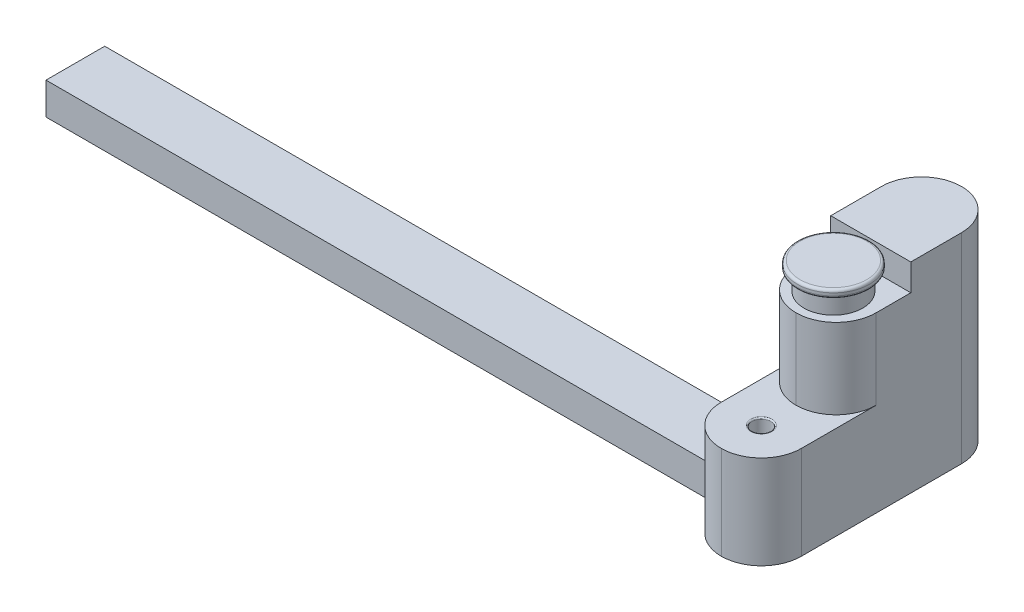
SolidWorks part; units mm, degrees
ref_plane "Front Plane" through (0, 0, 0) normal (0, 0, 1) x (1, 0, 0)
ref_plane "Top Plane" through (0, 0, 0) normal (0, 1, 0) x (1, 0, 0)
ref_plane "Right Plane" through (0, 0, 0) normal (1, 0, 0) x (0, 0, -1)
sketch "Sketch1" plane through (0, 0, 0) normal (1, 0, 0) x (0, 0, -1)
  line L1 (0, 0) -> (11, 0)
  line L2 (0, 0) -> (0, -6)
  line L3 (0, -6) -> (11, -6)
  line L4 (11, 0) -> (11, -6)
  dimension "D1" = 11
  dimension "D2" = 6
extrude "Boss-Extrude1" add sketch "Sketch1" along normal blind 124 from offset 73.5 offset against normal yes
sketch "Sketch2" plane through (50.5, 0, 0) normal (1, 0, 0) x (0, 0, -1)
  line L9 (-5, -9) -> (40, -9)
  line L10 (-5, -9) -> (-5, 28.5)
  line L11 (-5, 28.5) -> (40, 28.5)
  line L12 (40, -9) -> (40, 28.5)
  line L13 (-5, 8.5) -> (9, 8.5)
  line L14 (-5, 8.5) -> (-5, 28.5)
  line L15 (-5, 28.5) -> (9, 28.5)
  line L16 (9, 8.5) -> (9, 23.5)
  line L17 (9, 23.5) -> (23, 23.5)
  line L19 (9, 28.5) -> (23, 28.5)
  line L20 (23, 23.5) -> (23, 28.5)
  line M1 (0, 0) -> (0, -6)
  line M2 (0, -6) -> (11, -6)
  line M3 (11, -6) -> (11, 0)
  line M4 (11, 0) -> (0, 0)
  dimension "D1" = 5
  dimension "D2" = 9
  dimension "D3" = 37.5
  dimension "D4" = 45
  dimension "D5" = 14
  dimension "D6" = 14
  dimension "D7" = 5
  dimension "D8" = 15
extrude "Boss-Extrude3" add sketch "Sketch2" along normal blind 15 contours M4 M1 M2 M3 | L20 L17 L16 L13 L10 L9 L12 L11 M1 M4 M3 M2 region at (50.5, 7.5903, -21.6188) region at (50.5, -3, -5.5)
fillet "Fillet1" radius 7.5 6 edges at (50.5, -0.25, 5) (65.5, -0.25, 5) (50.5, 16, -9) (65.5, 16, -9) (50.5, 9.75, -40) (65.5, 9.75, -40)
sketch "Sketch4" plane through (0, 23.5, 0) normal (0, 1, 0) x (1, 0, 0)
  line L0 (50.5, 16.5) -> (50.5, 23) construction
  line L1 (65.5, 23) -> (50.5, 23) construction
  circle A0 centre (58, 16) radius 5.5
  dimension "D1" = 11
  dimension "D2" = 7.5
  dimension "D3" = 7
extrude "Boss-Extrude4" add sketch "Sketch4" along normal blind 5
sketch "Sketch5" plane through (0, 28.5, 0) normal (0, 1, 0) x (1, 0, 0)
  circle A0 centre (58, 16) radius 6.75
  dimension "D1" = 13.5
extrude "Boss-Extrude5" add sketch "Sketch5" against normal blind 1.5
fillet "Fillet2" radius 0.5 2 edges at (58, 28.5, -9.25) (58, 27, -9.25)
sketch "Sketch6" plane through (0, 8.5, 0) normal (0, 1, 0) x (1, 0, 0)
  circle A0 centre (58, 2.5) radius 1.75
  dimension "D1" = 3.5
extrude "Cut-Extrude1" cut sketch "Sketch6" against normal blind 3
fillet "Fillet3" radius 0.25 2 edges at (58, 5.5, -0.75) (58, 8.5, -0.75)
